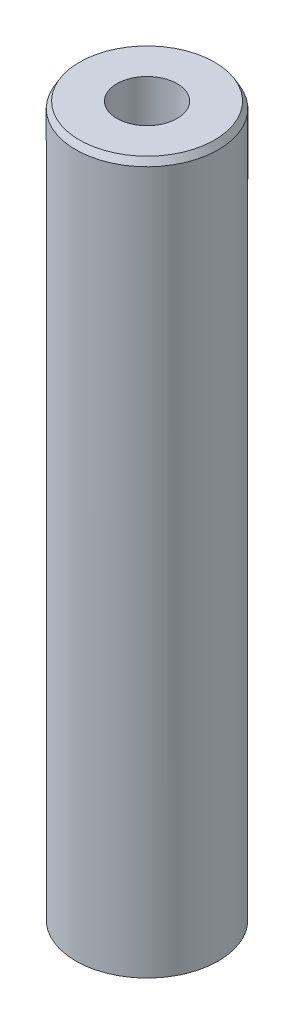
SolidWorks part; units mm, degrees
ref_plane "Front Plane" through (0, 0, 0) normal (0, 0, 1) x (1, 0, 0)
ref_plane "Top Plane" through (0, 0, 0) normal (0, 1, 0) x (1, 0, 0)
ref_plane "Right Plane" through (0, 0, 0) normal (1, 0, 0) x (0, 0, -1)
sketch "Sketch1" plane through (0, 0, 0) normal (0, 1, 0) x (1, 0, 0)
  circle A0 centre (0, 0) radius 60
  dimension "SHAFT_OD" = 120
extrude "Boss-Extrude1" add sketch "Sketch1" along normal blind 600
sketch "Sketch2" plane through (0, 0, 0) normal (0, 1, 0) x (1, 0, 0)
  circle A0 centre (0, 0) radius 25.3808
  dimension "BORE_D" = 50.7617
extrude "Cut-Extrude1" cut sketch "Sketch2" along normal through all
chamfer "Chamfer1" distance 5.4818 angle 30 2 edges at (0, 600, 60) (0, 0, 60) first distance on face at (0, 600, 60) first distance on face at (0, 0, 25.3808)
